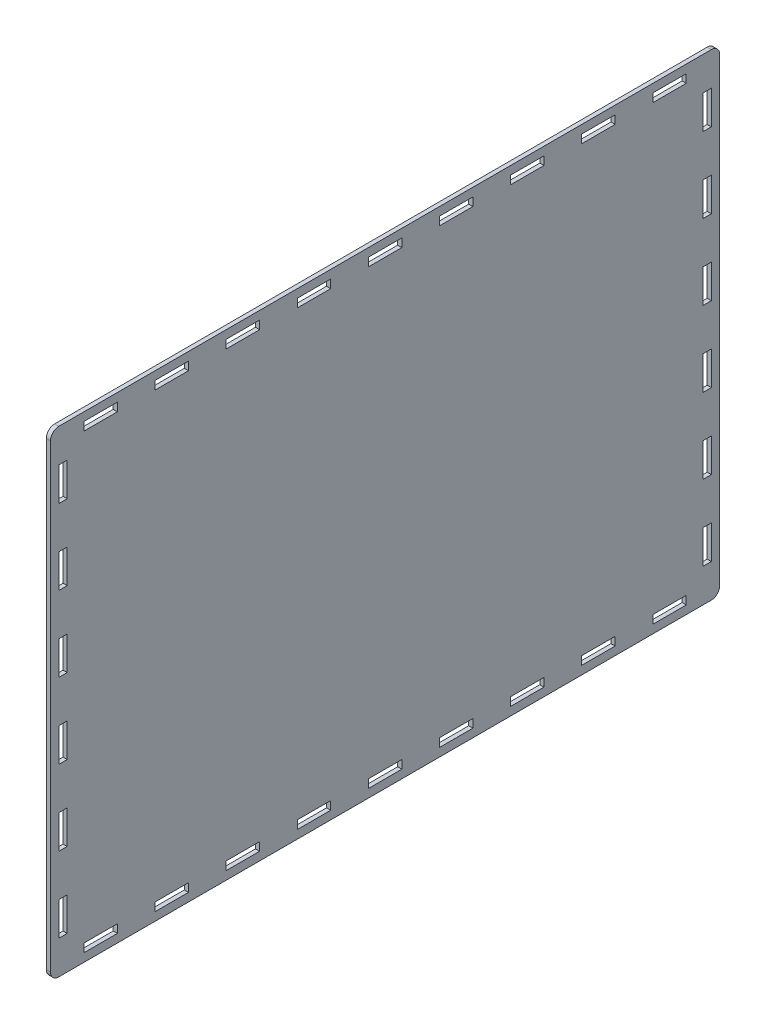
SolidWorks part; units mm, degrees
material "Mahogany"
ref_plane "Front" through (0, 0, 0) normal (0, 0, 1) x (1, 0, 0)
ref_plane "Top" through (0, 0, 0) normal (0, 1, 0) x (1, 0, 0)
ref_plane "Right" through (0, 0, 0) normal (1, 0, 0) x (0, 0, -1)
sketch "Sketch1" plane through (0, 0, 0) normal (1, 0, 0) x (0, 0, -1)
  line L0 (-195, -137.5) -> (-195, 137.5) construction
  line L1 (-200, -142.5) -> (200, -142.5)
  line L2 (-200, -142.5) -> (-200, 142.5)
  line L3 (-200, 142.5) -> (200, 142.5)
  line L4 (200, -142.5) -> (200, 142.5)
  line L5 (-200, -142.5) -> (200, 142.5) construction
  line L6 (-200, 142.5) -> (200, -142.5) construction
  line L7 (-195, 137.5) -> (195, 137.5) construction
  line L8 (195, -137.5) -> (195, 137.5) construction
  line L9 (-195, -137.5) -> (195, -137.5) construction
  line L10 (-190, -132.5) -> (-190, 132.5) construction
  line L11 (-190, 132.5) -> (190, 132.5) construction
  line L12 (190, -132.5) -> (190, 132.5) construction
  line L13 (-190, -132.5) -> (190, -132.5) construction
  line L14 (115, 69.5) -> (185, 69.5) construction
  line L15 (115, 67.5) -> (185, 67.5) construction
  line L16 (115, 67.5) -> (115, 127.5) construction
  line L17 (115, 127.5) -> (185, 127.5) construction
  line L18 (185, 67.5) -> (185, 127.5) construction
  line L19 (115, 67.5) -> (185, 127.5) construction
  line L20 (115, 127.5) -> (185, 67.5) construction
  line L21 (182.5, 127.5) -> (182.5, 67.5) construction
  line L22 (150, 107.4084) -> (150, 89.6954) construction
  line L23 (117.5, 127.5) -> (117.5, 67.5) construction
  line L24 (115, 67.5) -> (115, 127.5)
  line L25 (115, 127.5) -> (185, 127.5)
  line L26 (185, 127.5) -> (185, 67.5)
  line L27 (185, 67.5) -> (182.5, 67.5)
  line L28 (182.5, 67.5) -> (182.5, 69.5)
  line L29 (117.5, 67.5) -> (117.5, 69.5)
  line L30 (117.5, 69.5) -> (182.5, 69.5)
  line L31 (117.5, 67.5) -> (115, 67.5)
  line L32 (117.5, 2.5) -> (115, 2.5)
  line L33 (115, 2.5) -> (115, 62.5)
  line L34 (115, 62.5) -> (185, 62.5)
  line L35 (185, 62.5) -> (185, 2.5)
  line L36 (185, 2.5) -> (182.5, 2.5)
  line L37 (182.5, 2.5) -> (182.5, 4.5)
  line L38 (117.5, 4.5) -> (182.5, 4.5)
  line L39 (117.5, 2.5) -> (117.5, 4.5)
  line L40 (117.5, -62.5) -> (115, -62.5)
  line L41 (115, -62.5) -> (115, -2.5)
  line L42 (115, -2.5) -> (185, -2.5)
  line L43 (185, -2.5) -> (185, -62.5)
  line L44 (185, -62.5) -> (182.5, -62.5)
  line L45 (182.5, -62.5) -> (182.5, -60.5)
  line L46 (117.5, -60.5) -> (182.5, -60.5)
  line L47 (117.5, -62.5) -> (117.5, -60.5)
  line L48 (117.5, -127.5) -> (115, -127.5)
  line L49 (115, -127.5) -> (115, -67.5)
  line L50 (115, -67.5) -> (185, -67.5)
  line L51 (185, -67.5) -> (185, -127.5)
  line L52 (185, -127.5) -> (182.5, -127.5)
  line L53 (182.5, -127.5) -> (182.5, -125.5)
  line L54 (117.5, -125.5) -> (182.5, -125.5)
  line L55 (117.5, -127.5) -> (117.5, -125.5)
  line L56 (42.5, 67.5) -> (40, 67.5)
  line L57 (40, 67.5) -> (40, 127.5)
  line L58 (40, 127.5) -> (110, 127.5)
  line L59 (110, 127.5) -> (110, 67.5)
  line L60 (110, 67.5) -> (107.5, 67.5)
  line L61 (107.5, 67.5) -> (107.5, 69.5)
  line L62 (42.5, 69.5) -> (107.5, 69.5)
  line L63 (42.5, 67.5) -> (42.5, 69.5)
  line L64 (42.5, 2.5) -> (40, 2.5)
  line L65 (40, 2.5) -> (40, 62.5)
  line L66 (40, 62.5) -> (110, 62.5)
  line L67 (110, 62.5) -> (110, 2.5)
  line L68 (110, 2.5) -> (107.5, 2.5)
  line L69 (107.5, 2.5) -> (107.5, 4.5)
  line L70 (42.5, 4.5) -> (107.5, 4.5)
  line L71 (42.5, 2.5) -> (42.5, 4.5)
  line L72 (42.5, -62.5) -> (40, -62.5)
  line L73 (40, -62.5) -> (40, -2.5)
  line L74 (40, -2.5) -> (110, -2.5)
  line L75 (110, -2.5) -> (110, -62.5)
  line L76 (110, -62.5) -> (107.5, -62.5)
  line L77 (107.5, -62.5) -> (107.5, -60.5)
  line L78 (42.5, -60.5) -> (107.5, -60.5)
  line L79 (42.5, -62.5) -> (42.5, -60.5)
  line L80 (42.5, -127.5) -> (40, -127.5)
  line L81 (40, -127.5) -> (40, -67.5)
  line L82 (40, -67.5) -> (110, -67.5)
  line L83 (110, -67.5) -> (110, -127.5)
  line L84 (110, -127.5) -> (107.5, -127.5)
  line L85 (107.5, -127.5) -> (107.5, -125.5)
  line L86 (42.5, -125.5) -> (107.5, -125.5)
  line L87 (42.5, -127.5) -> (42.5, -125.5)
  line L88 (-32.5, 67.5) -> (-35, 67.5)
  line L89 (-35, 67.5) -> (-35, 127.5)
  line L90 (-35, 127.5) -> (35, 127.5)
  line L91 (35, 127.5) -> (35, 67.5)
  line L92 (35, 67.5) -> (32.5, 67.5)
  line L93 (32.5, 67.5) -> (32.5, 69.5)
  line L94 (-32.5, 69.5) -> (32.5, 69.5)
  line L95 (-32.5, 67.5) -> (-32.5, 69.5)
  line L96 (-32.5, 2.5) -> (-35, 2.5)
  line L97 (-35, 2.5) -> (-35, 62.5)
  line L98 (-35, 62.5) -> (35, 62.5)
  line L99 (35, 62.5) -> (35, 2.5)
  line L100 (35, 2.5) -> (32.5, 2.5)
  line L101 (32.5, 2.5) -> (32.5, 4.5)
  line L102 (-32.5, 4.5) -> (32.5, 4.5)
  line L103 (-32.5, 2.5) -> (-32.5, 4.5)
  line L104 (-32.5, -62.5) -> (-35, -62.5)
  line L105 (-35, -62.5) -> (-35, -2.5)
  line L106 (-35, -2.5) -> (35, -2.5)
  line L107 (35, -2.5) -> (35, -62.5)
  line L108 (35, -62.5) -> (32.5, -62.5)
  line L109 (32.5, -62.5) -> (32.5, -60.5)
  line L110 (-32.5, -60.5) -> (32.5, -60.5)
  line L111 (-32.5, -62.5) -> (-32.5, -60.5)
  line L112 (-32.5, -127.5) -> (-35, -127.5)
  line L113 (-35, -127.5) -> (-35, -67.5)
  line L114 (-35, -67.5) -> (35, -67.5)
  line L115 (35, -67.5) -> (35, -127.5)
  line L116 (35, -127.5) -> (32.5, -127.5)
  line L117 (32.5, -127.5) -> (32.5, -125.5)
  line L118 (-32.5, -125.5) -> (32.5, -125.5)
  line L119 (-32.5, -127.5) -> (-32.5, -125.5)
  line L120 (-107.5, 67.5) -> (-110, 67.5)
  line L121 (-110, 67.5) -> (-110, 127.5)
  line L122 (-110, 127.5) -> (-40, 127.5)
  line L123 (-40, 127.5) -> (-40, 67.5)
  line L124 (-40, 67.5) -> (-42.5, 67.5)
  line L125 (-42.5, 67.5) -> (-42.5, 69.5)
  line L126 (-107.5, 69.5) -> (-42.5, 69.5)
  line L127 (-107.5, 67.5) -> (-107.5, 69.5)
  line L128 (-107.5, 2.5) -> (-110, 2.5)
  line L129 (-110, 2.5) -> (-110, 62.5)
  line L130 (-110, 62.5) -> (-40, 62.5)
  line L131 (-40, 62.5) -> (-40, 2.5)
  line L132 (-40, 2.5) -> (-42.5, 2.5)
  line L133 (-42.5, 2.5) -> (-42.5, 4.5)
  line L134 (-107.5, 4.5) -> (-42.5, 4.5)
  line L135 (-107.5, 2.5) -> (-107.5, 4.5)
  line L136 (-107.5, -62.5) -> (-110, -62.5)
  line L137 (-110, -62.5) -> (-110, -2.5)
  line L138 (-110, -2.5) -> (-40, -2.5)
  line L139 (-40, -2.5) -> (-40, -62.5)
  line L140 (-40, -62.5) -> (-42.5, -62.5)
  line L141 (-42.5, -62.5) -> (-42.5, -60.5)
  line L142 (-107.5, -60.5) -> (-42.5, -60.5)
  line L143 (-107.5, -62.5) -> (-107.5, -60.5)
  line L144 (-107.5, -127.5) -> (-110, -127.5)
  line L145 (-110, -127.5) -> (-110, -67.5)
  line L146 (-110, -67.5) -> (-40, -67.5)
  line L147 (-40, -67.5) -> (-40, -127.5)
  line L148 (-40, -127.5) -> (-42.5, -127.5)
  line L149 (-42.5, -127.5) -> (-42.5, -125.5)
  line L150 (-107.5, -125.5) -> (-42.5, -125.5)
  line L151 (-107.5, -127.5) -> (-107.5, -125.5)
  line L152 (-182.5, 67.5) -> (-185, 67.5)
  line L153 (-185, 67.5) -> (-185, 127.5)
  line L154 (-185, 127.5) -> (-115, 127.5)
  line L155 (-115, 127.5) -> (-115, 67.5)
  line L156 (-115, 67.5) -> (-117.5, 67.5)
  line L157 (-117.5, 67.5) -> (-117.5, 69.5)
  line L158 (-182.5, 69.5) -> (-117.5, 69.5)
  line L159 (-182.5, 67.5) -> (-182.5, 69.5)
  line L160 (-182.5, 2.5) -> (-185, 2.5)
  line L161 (-185, 2.5) -> (-185, 62.5)
  line L162 (-185, 62.5) -> (-115, 62.5)
  line L163 (-115, 62.5) -> (-115, 2.5)
  line L164 (-115, 2.5) -> (-117.5, 2.5)
  line L165 (-117.5, 2.5) -> (-117.5, 4.5)
  line L166 (-182.5, 4.5) -> (-117.5, 4.5)
  line L167 (-182.5, 2.5) -> (-182.5, 4.5)
  line L168 (-182.5, -62.5) -> (-185, -62.5)
  line L169 (-185, -62.5) -> (-185, -2.5)
  line L170 (-185, -2.5) -> (-115, -2.5)
  line L171 (-115, -2.5) -> (-115, -62.5)
  line L172 (-115, -62.5) -> (-117.5, -62.5)
  line L173 (-117.5, -62.5) -> (-117.5, -60.5)
  line L174 (-182.5, -60.5) -> (-117.5, -60.5)
  line L175 (-182.5, -62.5) -> (-182.5, -60.5)
  line L176 (-182.5, -127.5) -> (-185, -127.5)
  line L177 (-185, -127.5) -> (-185, -67.5)
  line L178 (-185, -67.5) -> (-115, -67.5)
  line L179 (-115, -67.5) -> (-115, -127.5)
  line L180 (-115, -127.5) -> (-117.5, -127.5)
  line L181 (-117.5, -127.5) -> (-117.5, -125.5)
  line L182 (-182.5, -125.5) -> (-117.5, -125.5)
  line L183 (-182.5, -127.5) -> (-182.5, -125.5)
  line L184 (22.0868, 0) -> (-20.3756, 0) construction
  line L185 (-180, 137.5) -> (-160, 137.5)
  line L186 (-180, 137.5) -> (-180, 132.5)
  line L187 (-180, 132.5) -> (-160, 132.5)
  line L188 (-160, 137.5) -> (-160, 132.5)
  line L189 (-180, 137.5) -> (-160, 132.5) construction
  line L190 (-180, 132.5) -> (-160, 137.5) construction
  line L191 (0, 22.637) -> (0, -7.6263) construction
  line L192 (-180, -132.5) -> (-160, -132.5)
  line L193 (-160, -137.5) -> (-160, -132.5)
  line L194 (-180, -137.5) -> (-160, -137.5)
  line L195 (-180, -137.5) -> (-180, -132.5)
  line L196 (-137.5, 137.5) -> (-137.5, 132.5)
  line L197 (-137.5, 137.5) -> (-117.5, 137.5)
  line L198 (-117.5, 137.5) -> (-117.5, 132.5)
  line L199 (-137.5, 132.5) -> (-117.5, 132.5)
  line L200 (-137.5, -132.5) -> (-117.5, -132.5)
  line L201 (-117.5, -137.5) -> (-117.5, -132.5)
  line L202 (-137.5, -137.5) -> (-117.5, -137.5)
  line L203 (-137.5, -137.5) -> (-137.5, -132.5)
  line L204 (-95, 137.5) -> (-95, 132.5)
  line L205 (-95, 137.5) -> (-75, 137.5)
  line L206 (-75, 137.5) -> (-75, 132.5)
  line L207 (-95, 132.5) -> (-75, 132.5)
  line L208 (-95, -132.5) -> (-75, -132.5)
  line L209 (-75, -137.5) -> (-75, -132.5)
  line L210 (-95, -137.5) -> (-75, -137.5)
  line L211 (-95, -137.5) -> (-95, -132.5)
  line L212 (-52.5, 137.5) -> (-52.5, 132.5)
  line L213 (-52.5, 137.5) -> (-32.5, 137.5)
  line L214 (-32.5, 137.5) -> (-32.5, 132.5)
  line L215 (-52.5, 132.5) -> (-32.5, 132.5)
  line L216 (-52.5, -132.5) -> (-32.5, -132.5)
  line L217 (-32.5, -137.5) -> (-32.5, -132.5)
  line L218 (-52.5, -137.5) -> (-32.5, -137.5)
  line L219 (-52.5, -137.5) -> (-52.5, -132.5)
  line L220 (-10, 137.5) -> (-10, 132.5)
  line L221 (-10, 137.5) -> (10, 137.5)
  line L222 (10, 137.5) -> (10, 132.5)
  line L223 (-10, 132.5) -> (10, 132.5)
  line L224 (-10, -132.5) -> (10, -132.5)
  line L225 (10, -137.5) -> (10, -132.5)
  line L226 (-10, -137.5) -> (10, -137.5)
  line L227 (-10, -137.5) -> (-10, -132.5)
  line L228 (32.5, 137.5) -> (32.5, 132.5)
  line L229 (32.5, 137.5) -> (52.5, 137.5)
  line L230 (52.5, 137.5) -> (52.5, 132.5)
  line L231 (32.5, 132.5) -> (52.5, 132.5)
  line L232 (32.5, -132.5) -> (52.5, -132.5)
  line L233 (52.5, -137.5) -> (52.5, -132.5)
  line L234 (32.5, -137.5) -> (52.5, -137.5)
  line L235 (32.5, -137.5) -> (32.5, -132.5)
  line L236 (75, 137.5) -> (75, 132.5)
  line L237 (75, 137.5) -> (95, 137.5)
  line L238 (95, 137.5) -> (95, 132.5)
  line L239 (75, 132.5) -> (95, 132.5)
  line L240 (75, -132.5) -> (95, -132.5)
  line L241 (95, -137.5) -> (95, -132.5)
  line L242 (75, -137.5) -> (95, -137.5)
  line L243 (75, -137.5) -> (75, -132.5)
  line L244 (117.5, 137.5) -> (117.5, 132.5)
  line L245 (117.5, 137.5) -> (137.5, 137.5)
  line L246 (137.5, 137.5) -> (137.5, 132.5)
  line L247 (117.5, 132.5) -> (137.5, 132.5)
  line L248 (117.5, -132.5) -> (137.5, -132.5)
  line L249 (137.5, -137.5) -> (137.5, -132.5)
  line L250 (117.5, -137.5) -> (137.5, -137.5)
  line L251 (117.5, -137.5) -> (117.5, -132.5)
  line L252 (160, 137.5) -> (160, 132.5)
  line L253 (160, 137.5) -> (180, 137.5)
  line L254 (180, 137.5) -> (180, 132.5)
  line L255 (160, 132.5) -> (180, 132.5)
  line L256 (160, -132.5) -> (180, -132.5)
  line L257 (180, -137.5) -> (180, -132.5)
  line L258 (160, -137.5) -> (180, -137.5)
  line L259 (160, -137.5) -> (160, -132.5)
  line L260 (190, 102.5) -> (195, 102.5)
  line L261 (-190, 122.5) -> (-195, 122.5)
  line L262 (-190, 122.5) -> (-190, 102.5)
  line L263 (-190, 102.5) -> (-195, 102.5)
  line L264 (-195, 122.5) -> (-195, 102.5)
  line L265 (-190, 122.5) -> (-195, 102.5) construction
  line L266 (-190, 102.5) -> (-195, 122.5) construction
  line L267 (195, 122.5) -> (195, 102.5)
  line L268 (190, 122.5) -> (195, 122.5)
  line L269 (190, 122.5) -> (190, 102.5)
  line L270 (-190, 77.5) -> (-190, 57.5)
  line L271 (-190, 77.5) -> (-195, 77.5)
  line L272 (-195, 77.5) -> (-195, 57.5)
  line L273 (-190, 57.5) -> (-195, 57.5)
  line L274 (190, 57.5) -> (195, 57.5)
  line L275 (195, 77.5) -> (195, 57.5)
  line L276 (190, 77.5) -> (195, 77.5)
  line L277 (190, 77.5) -> (190, 57.5)
  line L278 (-190, 32.5) -> (-190, 12.5)
  line L279 (-190, 32.5) -> (-195, 32.5)
  line L280 (-195, 32.5) -> (-195, 12.5)
  line L281 (-190, 12.5) -> (-195, 12.5)
  line L282 (190, 12.5) -> (195, 12.5)
  line L283 (195, 32.5) -> (195, 12.5)
  line L284 (190, 32.5) -> (195, 32.5)
  line L285 (190, 32.5) -> (190, 12.5)
  line L286 (-190, -12.5) -> (-190, -32.5)
  line L287 (-190, -12.5) -> (-195, -12.5)
  line L288 (-195, -12.5) -> (-195, -32.5)
  line L289 (-190, -32.5) -> (-195, -32.5)
  line L290 (190, -32.5) -> (195, -32.5)
  line L291 (195, -12.5) -> (195, -32.5)
  line L292 (190, -12.5) -> (195, -12.5)
  line L293 (190, -12.5) -> (190, -32.5)
  line L294 (-190, -57.5) -> (-190, -77.5)
  line L295 (-190, -57.5) -> (-195, -57.5)
  line L296 (-195, -57.5) -> (-195, -77.5)
  line L297 (-190, -77.5) -> (-195, -77.5)
  line L298 (190, -77.5) -> (195, -77.5)
  line L299 (195, -57.5) -> (195, -77.5)
  line L300 (190, -57.5) -> (195, -57.5)
  line L301 (190, -57.5) -> (190, -77.5)
  line L302 (-190, -102.5) -> (-190, -122.5)
  line L303 (-190, -102.5) -> (-195, -102.5)
  line L304 (-195, -102.5) -> (-195, -122.5)
  line L305 (-190, -122.5) -> (-195, -122.5)
  line L306 (190, -122.5) -> (195, -122.5)
  line L307 (195, -102.5) -> (195, -122.5)
  line L308 (190, -102.5) -> (195, -102.5)
  line L309 (190, -102.5) -> (190, -122.5)
  point P0 (0, 0)
  point P14 (150, 97.5)
  point P185 (-170, 135)
  point P262 (-192.5, 112.5)
  dimension "D3" = 400
  dimension "D4" = 285
  dimension "D5" = 70
  dimension "D6" = 60
  dimension "D7" = 2.5
  dimension "D8" = 2
  dimension "D9" = 5
  dimension "D10" = 5
  dimension "D12" = 5
  dimension "D13" = 5
  dimension "D14" = 5
  dimension "D15" = 20
  dimension "D16" = 20
  dimension "D18" = 20
  dimension "D19" = 20
  dimension "D21" = 20
  dimension "D1" = 5
  dimension "D2" = 5
  dimension "D11" = 4
  dimension "D17" = 9
  dimension "D20" = 6
extrude "Boss-Extrude2" [suppressed] add sketch "Sketch1" along normal blind 2.5
extrude "Boss-Extrude3" add sketch "Sketch1<2>" along normal blind 2.5 contours L1 L4 L3 L2 L309 L308 L307 L306 L301 L300 L299 L298 L293 L292 L291 L290 L285 L284 L283 L282 L277 L276 L275 L274 L269 L268 L267 L260 L264 L261 L262 L263 L255 L252 L253 L254 L247 L244 L245 L246 L239 | L176 L183 L182 L181 L180 L179 L178 L177 | L168 L175 L174 L173 L172 L171 L170 L169 | L160 L167 L166 L165 L164 L163 L162 L161 | L152 L159 L158 L157 L156 L155 L154 L153 | L120 L127 L126 L125 L124 L123 L122 L121 | L88 L95 L94 L93 L92 L91 L90 L89 | L56 L63 L62 L61 L60 L59 L58 L57 | L31 L29 L30 L28 L27 L26 L25 L24 | L32 L39 L38 L37 L36 L35 L34 L33 | L64 L71 L70 L69 L68 L67 L66 L65 | L96 L103 L102 L101 L100 L99 L98 L97 | L128 L135 L134 L133 L132 L131 L130 L129 | L136 L143 L142 L141 L140 L139 L138 L137 | L104 L111 L110 L109 L108 L107 L106 L105 | L72 L79 L78 L77 L76 L75 L74 L73 | L40 L47 L46 L45 L44 L43 L42 L41 | L48 L55 L54 L53 L52 L51 L50 L49 | L80 L87 L86 L85 L84 L83 L82 L81 | L112 L119 L118 L117 L116 L115 L114 L113 | L144 L151 L150 L149 L148 L147 L146 L145 region at (0, 0, 195.0885) region at (0, 98.4263, -150) region at (0, 33.4263, -150) region at (0, -31.5737, -150) region at (0, -96.5737, -150) region at (0, 98.4263, -75) region at (0, 33.4263, -75) region at (0, -31.5737, -75) region at (0, -96.5737, -75) region at (0, 98.4263, 0) region at (0, 33.4263, 0) region at (0, -31.5737, 0) region at (0, -96.5737, 0) region at (0, 98.4263, 75) region at (0, 33.4263, 75) region at (0, -31.5737, 75) region at (0, -96.5737, 75) region at (0, 98.4263, 150) region at (0, 33.4263, 150) region at (0, -31.5737, 150) region at (0, -96.5737, 150)
sketch "Sketch1<2>" plane through (0, 0, 0) normal (1, 0, 0) x (0, 0, -1) same geometry as "Sketch1"
fillet "Fillet1" [suppressed] radius 5
fillet "Fillet2" radius 5 4 edges at (1.25, -142.5, 200) (1.25, 142.5, -200) (1.25, -142.5, -200) (1.25, 142.5, 200)
